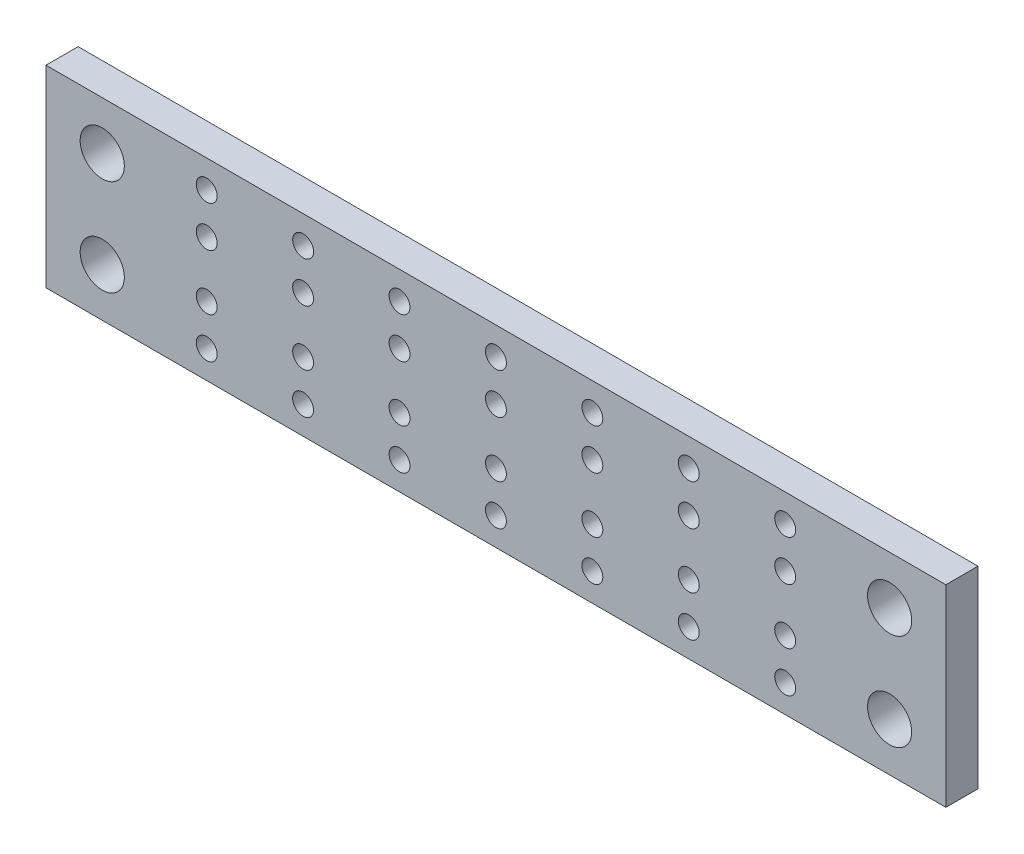
SolidWorks part; units mm, degrees
ref_plane "Front Plane" through (0, 0, 0) normal (0, 0, 1) x (1, 0, 0)
ref_plane "Top Plane" through (0, 0, 0) normal (0, 1, 0) x (1, 0, 0)
ref_plane "Right Plane" through (0, 0, 0) normal (1, 0, 0) x (0, 0, -1)
sketch "Sketch1" plane through (0, 0, 0) normal (0, 0, 1) x (1, 0, 0)
  line L1 (0, 0) -> (42, 0)
  line L2 (0, 0) -> (0, 12)
  line L3 (0, 12) -> (42, 12)
  line L4 (42, 0) -> (42, 12)
  dimension "D1" = 42
  dimension "D2" = 12
extrude "tailLightBase" add sketch "Sketch1" along normal blind 2
sketch "Sketch2" plane through (0, 0, 2) normal (0, 0, 1) x (1, 0, 0)
  line L0 (42, 12) -> (0, 12) construction
  line L1 (0, 12) -> (0, 0) construction
  line L2 (0, 6) -> (42, 6) construction
  line L3 (42, 0) -> (42, 12) construction
  line L4 (3, 7.73) -> (3, 10.27) construction
  line L5 (9, 7.73) -> (9, 10.27) construction
  line L6 (15, 7.73) -> (15, 10.27) construction
  line L7 (21, 7.73) -> (21, 10.27) construction
  line L8 (27, 7.73) -> (27, 10.27) construction
  line L9 (33, 7.73) -> (33, 10.27) construction
  line L10 (39, 7.73) -> (39, 10.27) construction
  circle A0 centre (3, 9) radius 3 construction
  circle A1 centre (9, 9) radius 3 construction
  circle A2 centre (15, 9) radius 3 construction
  circle A3 centre (21, 9) radius 3 construction
  circle A4 centre (27, 9) radius 3 construction
  circle A5 centre (33, 9) radius 3 construction
  circle A6 centre (39, 9) radius 3 construction
  circle A7 centre (39, 3) radius 3 construction
  circle A8 centre (33, 3) radius 3 construction
  circle A9 centre (27, 3) radius 3 construction
  circle A10 centre (21, 3) radius 3 construction
  circle A11 centre (15, 3) radius 3 construction
  circle A12 centre (9, 3) radius 3 construction
  circle A13 centre (3, 3) radius 3 construction
  circle A14 centre (3, 10.27) radius 0.65
  circle A15 centre (3, 7.73) radius 0.65
  circle A16 centre (9, 10.27) radius 0.65
  circle A17 centre (9, 7.73) radius 0.65
  circle A18 centre (15, 10.27) radius 0.65
  circle A19 centre (15, 7.73) radius 0.65
  circle A20 centre (21, 10.27) radius 0.65
  circle A21 centre (21, 7.73) radius 0.65
  circle A22 centre (27, 10.27) radius 0.65
  circle A23 centre (27, 7.73) radius 0.65
  circle A24 centre (33, 10.27) radius 0.65
  circle A25 centre (33, 7.73) radius 0.65
  circle A26 centre (39, 10.27) radius 0.65
  circle A27 centre (39, 7.73) radius 0.65
  circle A28 centre (39, 4.27) radius 0.65
  circle A29 centre (39, 1.73) radius 0.65
  circle A30 centre (33, 1.73) radius 0.65
  circle A31 centre (33, 4.27) radius 0.65
  circle A32 centre (27, 4.27) radius 0.65
  circle A33 centre (27, 1.73) radius 0.65
  circle A34 centre (21, 4.27) radius 0.65
  circle A35 centre (21, 1.73) radius 0.65
  circle A36 centre (15, 4.27) radius 0.65
  circle A37 centre (15, 1.73) radius 0.65
  circle A38 centre (9, 1.73) radius 0.65
  circle A39 centre (9, 4.27) radius 0.65
  circle A40 centre (3, 1.73) radius 0.65
  circle A41 centre (3, 4.27) radius 0.65
  point P41 (3, 9)
  dimension "D1" = 6
  dimension "D4" = 1.3
  dimension "D3" = 2.54
  dimension "D2" = 7
  dimension "D5" = 7
extrude "ledMounts" cut sketch "Sketch2" against normal blind 2
sketch "Sketch3" plane through (0, 0, 2) normal (0, 0, 1) x (1, 0, 0)
  line L0 (21, 0) -> (21, 12) construction
  line L1 (0, 12) -> (-7, 12)
  line L2 (0, 12) -> (0, 0)
  line L3 (0, 0) -> (-7, 0)
  line L4 (-7, 12) -> (-7, 0)
  line L5 (0, 0) -> (42, 0) construction
  line L6 (42, 12) -> (0, 12) construction
  line L7 (42, 0) -> (49, 0)
  line L8 (49, 12) -> (49, 0)
  line L9 (42, 12) -> (49, 12)
  line L10 (42, 12) -> (42, 0)
  dimension "D1" = 7
extrude "mountingTabs" add sketch "Sketch3" against normal up to surface (2 mm away) up to face at (27.65, 10.27, 0)
sketch "Sketch4" plane through (0, 0, 2) normal (0, 0, 1) x (1, 0, 0)
  line L0 (0, 6) -> (42, 6) construction
  line L3 (21, 0) -> (21, 12) construction
  line L4 (-7, 0) -> (49, 0) construction
  line L5 (0, 6) -> (0, 12) construction
  line L6 (0, 12) -> (0, 0) construction
  line L7 (0, 6) -> (0, 0) construction
  line L8 (42, 0) -> (42, 6) construction
  line L9 (42, 12) -> (42, 0) construction
  line L10 (42, 6) -> (42, 12) construction
  line L11 (0, 6) -> (-7, 6) construction
  line L12 (-7, 12) -> (-7, 0) construction
  line L13 (42, 6) -> (49, 6) construction
  line L14 (49, 12) -> (49, 0) construction
  circle A0 centre (-3.5, 9) radius 1.375
  circle A1 centre (45.5, 9) radius 1.375
  circle A2 centre (-3.5, 3) radius 1.375
  circle A3 centre (45.5, 3) radius 1.375
  point P0 (-3.5, 6)
  point P25 (0, 9)
  dimension "D1" = 2.75
extrude "mountingHoles" cut sketch "Sketch4" against normal blind 2
